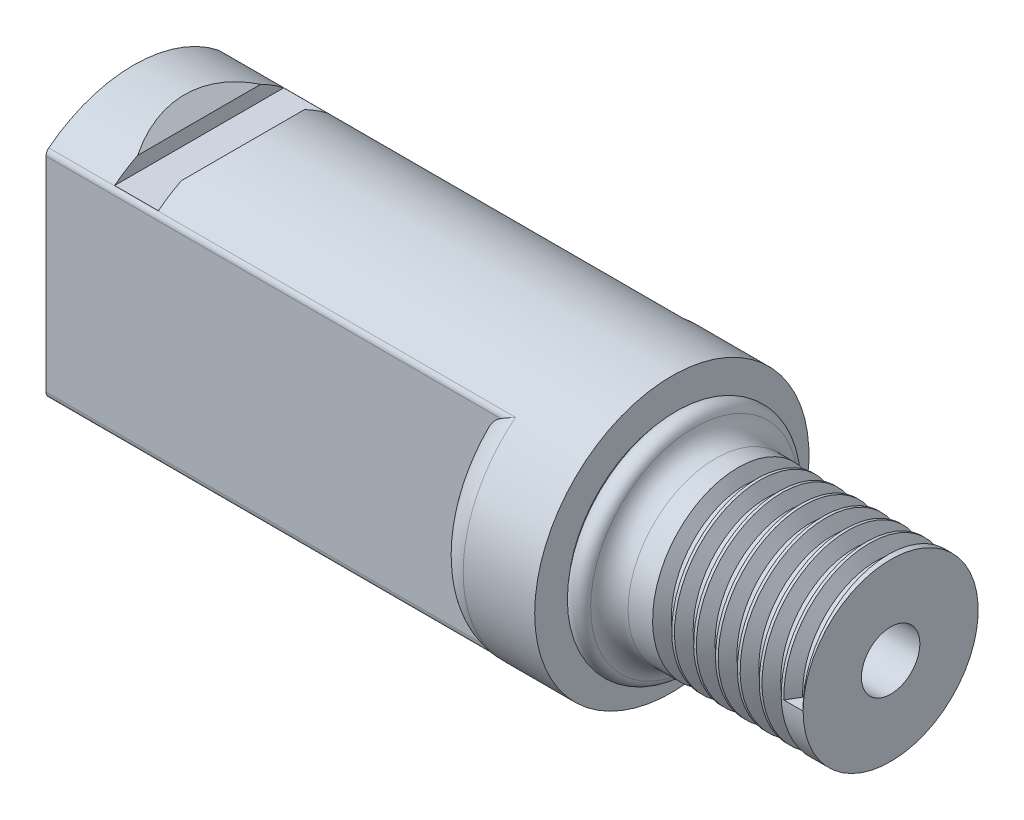
SolidWorks part; units mm, degrees
material "ABS"
ref_plane "Front Plane" through (0, 0, 0) normal (0, 0, 1) x (1, 0, 0)
ref_plane "Top Plane" through (0, 0, 0) normal (0, 1, 0) x (1, 0, 0)
ref_plane "Right Plane" through (0, 0, 0) normal (1, 0, 0) x (0, 0, -1)
sketch "Sketch2" plane through (0, 0, 0) normal (0, 0, 1) x (1, 0, 0)
  line L0 (0, 0) -> (51.9, 0) construction
  line L1 (51.9, 0) -> (51.9, -6)
  line L2 (51.9, -6) -> (39.9, -6)
  line L3 (37, -7.1159) -> (36.9, -7.1159)
  line L4 (36.9, -7.1159) -> (36.9, -9.4)
  line L5 (36.9, -9.4) -> (0, -9.4)
  line L6 (0, -9.4) -> (0, 0)
  line L7 (0, 0) -> (51.9, 0)
  arc A0 (39.9, -6) -> (38.45, -7.1159) centre (39.9, -7.5) ccw
  arc A1 (38.45, -7.1159) -> (37, -7.1159) centre (37.725, -6.9239) cw
  dimension "D4" = 1.5
  dimension "D5" = 0.75
  dimension "D1" = 51.9
  dimension "D2" = 6
  dimension "D3" = 12
  dimension "D6" = 9.4
  dimension "D7" = 0.1
  dimension "D8" = 36.9
revolve "Revolve1" add sketch "Sketch2" angle 360 about L0
sketch "Sketch3" plane through (0, 0, 0) normal (0, 0, 1) x (1, 0, 0)
  line L0 (3.5, 9.4) -> (4.5, 8.4)
  line L1 (36.9, 9.4) -> (0, 9.4) construction
  line L2 (4.5, 8.4) -> (4.5, 7.4)
  line L3 (4.5, 7.4) -> (7.5, 7.4)
  line L4 (7.5, 7.4) -> (7.5, 8.4)
  line L5 (7.5, 8.4) -> (8.5, 9.4)
  line L6 (8.5, 9.4) -> (3.5, 9.4)
  line L7 (0, 9.4) -> (0, -9.4) construction
  point P4 (6, 7.4)
  point P9 (6, 9.4)
  dimension "D1" = 2
  dimension "D2" = 1
  dimension "D3" = 3
  dimension "D4" = 3.5
extrude "Cut-Extrude2" cut sketch "Sketch3" against normal through all and the other way through all
mirror "Mirror1" about plane through (0, 0, 0) normal (0, 1, 0) of "Cut-Extrude2"
sketch "Sketch4" plane through (0, 0, 0) normal (-1, 0, 0) x (0, 0, 1)
  circle A0 centre (0, 0) radius 2.5
  circle A1 centre (0, 0) radius 5
  dimension "D1" = 5
  dimension "D2" = 10
extrude "Cut-Extrude3" cut sketch "Sketch4" against normal blind 10 contours A1 A0 | A0 | A1 region at (0, 0, 0) region at (0, 0, -4.8586)
extrude "Cut-Extrude4" cut sketch "Sketch4<3>" against normal blind 20 contours A0 region at (0, 0, 0)
sketch "Sketch4<3>" plane through (0, 0, 0) normal (-1, 0, 0) x (0, 0, 1) same geometry as "Sketch4"
sketch "Sketch5" plane through (20, 0, 0) normal (-1, 0, 0) x (0, 0, 1)
  circle A0 centre (0, 0) radius 2
  dimension "D1" = 4
extrude "Cut-Extrude5" cut sketch "Sketch5" against normal through all
thread "Thread1" pitch 1.5 method cut profile "Thread Profile1" start angle 0, offset 0, length 10, pitch 1.5, diameter 12
ref_plane "Plane1" through (51.9, 0, 6) normal (0, -1, 0) x (0, 0, 1)
sketch "Thread Profile1" plane through (51.9, 0, 6) normal (0, -1, 0) x (0, 0, 1)
  line L0 (0, 0) -> (0, 1.5) construction
  line L11 (0, 0) -> (0, 1.3125)
  line L12 (0, 1.3125) -> (-0.8119, 0.8437)
  line L13 (-0.8119, 0.8437) -> (-0.8119, 0.4687)
  line L15 (-0.8119, 0.4687) -> (0, 0)
  line L17 (-0.8119, 0.6562) -> (0, 0.6562) construction
  point P2 (0, 0)
  dimension "Pitch" = 1.5
  dimension "Profile_Angle" = 60
  dimension "Profile_Land" = 0.375
  dimension "Profile_Height" = 0.8119
sketch "Sketch8" plane through (0, 0, 0) normal (-1, 0, 0) x (0, 0, 1)
  line L0 (-6, 7.236) -> (-6, -7.236)
  line L1 (0, 9.4) -> (0, -9.4) construction
  line L2 (6, 7.236) -> (6, -7.236)
  circle A0 centre (0, 0) radius 9.4 construction
  arc A1 (6, -7.236) -> (6, 7.236) centre (0, 0) ccw
  circle A2 centre (0, 0) radius 9.4
  arc A3 (-6, 7.236) -> (-6, -7.236) centre (0, 0) ccw
  dimension "D1" = 6
  dimension "D2" = 0
extrude "Cut-Extrude6" cut sketch "Sketch8" against normal blind 30
fillet "Fillet1" radius 2 2 edges at (30, 0, -9.4) (30, 0, 9.4)
fillet "Fillet2" radius 0.5 5 edges at (0, 0, 5) (16, -7.236, -6) (16, -7.236, 6) (16, 7.236, 6) (16, 7.236, -6)
